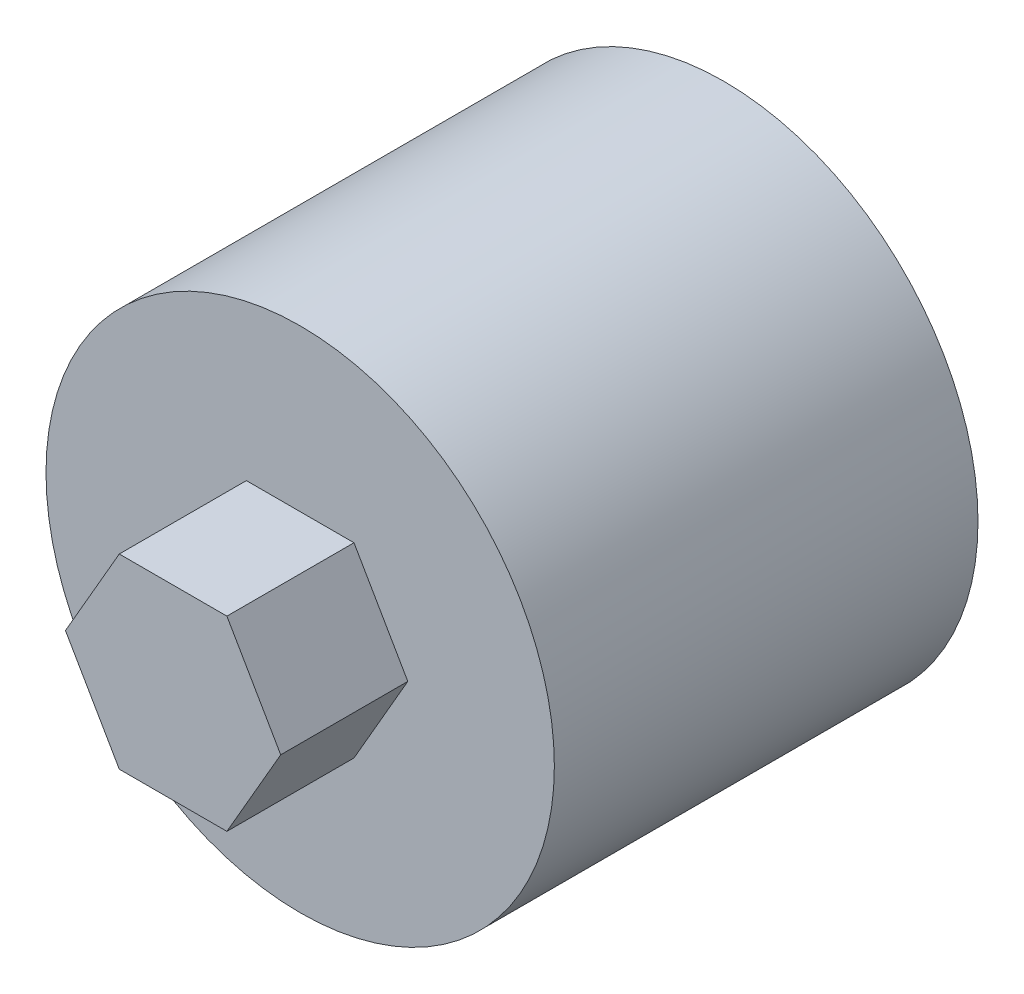
SolidWorks part; units mm, degrees
ref_plane "前视基准面" through (0, 0, 0) normal (0, 0, 1) x (1, 0, 0)
ref_plane "上视基准面" through (0, 0, 0) normal (0, 1, 0) x (1, 0, 0)
ref_plane "右视基准面" through (0, 0, 0) normal (1, 0, 0) x (0, 0, -1)
other "Configuration Table"
sketch "草图1" plane through (0, 0, 0) normal (0, 0, 1) x (1, 0, 0)
  line L0 (0, 0) -> (1.7387, 0.4659) construction
  line L1 (0, 0) -> (1.6291, 0.4551)
  line L2 (0, 0) -> (1.6291, -0.4551)
  line L3 (0, 0) -> (1.7387, -0.4659) construction
  line L4 (0, 0) -> (2.425, 0) construction
  line L5 (1.7387, 0.4659) -> (1.7387, -0.4659) construction
  circle A0 centre (0, 0) radius 1.525
  circle A1 centre (0, 0) radius 2.425
  circle A2 centre (0, 0) radius 1.6914 construction
  circle A3 centre (0, 0) radius 1.8 construction
  circle A4 centre (0, 0) radius 3
  spline S0 degree 4 poles (1.6291, 0.4551) (1.6415, 0.4586) (1.6769, 0.4656) (1.746, 0.4684) (1.8576, 0.4574) (1.9985, 0.4209) (2.171, 0.3489) (2.3582, 0.2351) (2.5438, 0.0819) (2.7191, -0.1093) (2.8693, -0.3205) (2.9946, -0.5472) (3.1006, -0.7975) (3.1986, -1.1195) (3.2658, -1.5159) (3.2754, -1.9832) (3.2064, -2.4974) (3.0631, -2.9965) (2.8558, -3.471) (2.5865, -3.9159) (2.2706, -4.3232) (1.901, -4.6937) (1.507, -5.0164) (1.0559, -5.3028) (0.6986, -5.4883) (0.2793, -5.6591) (0.0342, -5.7399) (-0.2484, -5.8241) (-0.3932, -5.8525) (-0.5197, -5.8826) (-0.5587, -5.8884) (-0.5863, -5.894) (-0.6011, -5.8971) knots 0 0 0 0 0 0.005604 0.015718 0.02996 0.048734 0.068727 0.096889 0.125051 0.153212 0.181374 0.209535 0.237696 0.271429 0.327752 0.384075 0.440398 0.496721 0.553044 0.609367 0.66569 0.722013 0.778336 0.834659 0.890982 0.909091 0.954545 0.977273 0.988636 0.994318 1 1 1 1 1 construction
  spline S1 degree 4 poles (1.6291, 0.4551) (1.6415, 0.4586) (1.6769, 0.4656) (1.746, 0.4684) (1.8576, 0.4574) (1.9985, 0.4209) (2.171, 0.3489) (2.3582, 0.2351) (2.5438, 0.0819) (2.7191, -0.1093) (2.8693, -0.3205) (2.9946, -0.5472) (3.1006, -0.7975) (3.1986, -1.1195) (3.2658, -1.5159) (3.2754, -1.9832) (3.2064, -2.4974) (3.0631, -2.9965) (2.8558, -3.471) (2.5865, -3.9159) (2.2706, -4.3232) (1.901, -4.6937) (1.507, -5.0164) (1.0559, -5.3028) (0.6986, -5.4883) (0.3874, -5.615) (0.2408, -5.6686) (0.2052, -5.6811) knots 0 0 0 0 0 0.005604 0.015718 0.02996 0.048734 0.068727 0.096889 0.125051 0.153212 0.181374 0.209535 0.237696 0.271429 0.327752 0.384075 0.440398 0.496721 0.553044 0.609367 0.66569 0.722013 0.778336 0.834659 0.890982 0.909091 0.909091 0.909091 0.909091 0.909091
  spline S2 degree 4 poles (1.6291, -0.4551) (1.6415, -0.4586) (1.6769, -0.4656) (1.746, -0.4684) (1.8576, -0.4574) (1.9985, -0.4209) (2.171, -0.3489) (2.3582, -0.2351) (2.5438, -0.0819) (2.7191, 0.1093) (2.8693, 0.3205) (2.9946, 0.5472) (3.1006, 0.7975) (3.1986, 1.1195) (3.2658, 1.5159) (3.2754, 1.9832) (3.2064, 2.4974) (3.0631, 2.9965) (2.8558, 3.471) (2.5865, 3.9159) (2.2706, 4.3232) (1.901, 4.6937) (1.507, 5.0164) (1.0559, 5.3028) (0.6986, 5.4883) (0.2793, 5.6591) (0.0342, 5.7399) (-0.2484, 5.8241) (-0.3932, 5.8525) (-0.5197, 5.8826) (-0.5587, 5.8884) (-0.5863, 5.894) (-0.6011, 5.8971) knots 0 0 0 0 0 0.005604 0.015718 0.02996 0.048734 0.068727 0.096889 0.125051 0.153212 0.181374 0.209535 0.237696 0.271429 0.327752 0.384075 0.440398 0.496721 0.553044 0.609367 0.66569 0.722013 0.778336 0.834659 0.890982 0.909091 0.954545 0.977273 0.988636 0.994318 1 1 1 1 1 construction
  spline S3 degree 4 poles (1.6291, -0.4551) (1.6415, -0.4586) (1.6769, -0.4656) (1.746, -0.4684) (1.8576, -0.4574) (1.9985, -0.4209) (2.171, -0.3489) (2.3582, -0.2351) (2.5438, -0.0819) (2.7191, 0.1093) (2.8693, 0.3205) (2.9946, 0.5472) (3.1006, 0.7975) (3.1986, 1.1195) (3.2658, 1.5159) (3.2754, 1.9832) (3.2064, 2.4974) (3.0631, 2.9965) (2.8558, 3.471) (2.5865, 3.9159) (2.2706, 4.3232) (1.901, 4.6937) (1.507, 5.0164) (1.0559, 5.3028) (0.6986, 5.4883) (0.3874, 5.615) (0.2408, 5.6686) (0.2052, 5.6811) knots 0 0 0 0 0 0.005604 0.015718 0.02996 0.048734 0.068727 0.096889 0.125051 0.153212 0.181374 0.209535 0.237696 0.271429 0.327752 0.384075 0.440398 0.496721 0.553044 0.609367 0.66569 0.722013 0.778336 0.834659 0.890982 0.909091 0.909091 0.909091 0.909091 0.909091
  point P16 (1.7387, 0)
  dimension "内啮合齿顶圆直径" = 3.05
  dimension "内啮合分度圆直径" = 3.6
  dimension "内啮合基圆直径" = 3.3829
  dimension "内啮合齿根圆直径" = 4.85
  dimension "外径" = 6
  dimension "渐开线镜像线夹角" = 15
extrude "凸台-拉伸1" add sketch "草图1" along normal blind 4 contours A4 | A0
extrude "切除-拉伸2" cut sketch "草图1<3>" along normal through all contours A0 S3 A1 S1 region at (1.9135, 0, 0)
sketch "草图1<3>" plane through (0, 0, 0) normal (0, 0, 1) x (1, 0, 0) same geometry as "草图1"
pattern_circular "阵列(圆周)1" count 9 over 360 about axis through (0, 0, 4) along (0, 0, 1) of "切除-拉伸2"
sketch "草图2" plane through (0, 0, 4) normal (0, 0, 1) x (1, 0, 0)
  line L1 (0.6351, 1.1) -> (-0.6351, 1.1)
  line L2 (-0.6351, 1.1) -> (-1.2702, 0)
  line L3 (-1.2702, 0) -> (-0.6351, -1.1)
  line L4 (-0.6351, -1.1) -> (0.6351, -1.1)
  line L5 (0.6351, -1.1) -> (1.2702, 0)
  line L6 (1.2702, 0) -> (0.6351, 1.1)
  circle A0 centre (0, 0) radius 3
  circle A1 centre (0, 0) radius 3 construction
  circle A2 centre (0, 0) radius 1.2702
  circle A3 centre (0, 0) radius 1.1 construction
  dimension "D1" = 2.2
extrude "凸台-拉伸2" add sketch "草图2" along normal blind 1 contours A0
extrude "凸台-拉伸3" add sketch "草图2<3>" along normal blind 1.5 from surface contours L1 L2 L3 L4 L5 L6 starting at face at (3, 0, 5)
sketch "草图2<3>" plane through (0, 0, 4) normal (0, 0, 1) x (1, 0, 0) same geometry as "草图2"
equation "\"m\"= 0.4'模数"
equation "\"z1\"= 6'外啮合齿轮数"
equation "\"a\"= 20度'压力角"
equation "\"z2\"= 9'内啮合齿轮数"
equation "\"hax\"= 1'齿顶高系数"
equation "\"cx\"= 0.25'顶隙系数"
equation "\"ha\"= \"hax\" * \"m\"'齿顶高"
equation "\"hf\"= ( \"hax\" + \"cx\" ) * \"m\"'齿根高"
equation "\"d1\"= \"m\" * \"z1\"'外啮合分度圆直径"
equation "\"da1\"= ( \"z1\" + 2 ) * \"m\"'外啮合齿顶圆直径"
equation "\"df1\"= \"d1\" - 2 * \"hf\"'外啮合齿根圆直径"
equation "\"db1\"= \"d1\" * cos ( \"a\" )'外啮合基圆直径"
equation "\"p\"= \"m\" * PI'齿距"
equation "\"d2\"= \"m\" * \"z2\"'内啮合分度圆直径"
equation "\"db2\"= \"d2\" * cos ( \"a\" )'内啮合基圆直径"
equation "\"da2\"= ( \"z2\" - 2 ) * \"m\"'内啮合齿顶圆直径"
equation "\"df2\"= \"d2\" + 2 * \"hf\"'内啮合齿根圆直径"
equation "\"内啮合齿顶圆直径@草图1\" = \"da2\" + 0.5 * \"hf\""
equation "\"内啮合齿根圆直径@草图1\"= \"df2\" + 0.5 * \"hf\""
equation "\"内啮合分度圆直径@草图1\"= \"d2\""
equation "\"内啮合基圆直径@草图1\"= \"db2\""
equation "\"渐开线镜像线夹角@草图1\"= 360度 / 4 / \"z2\" + 360度 / 4 / \"z2\" / 2"
equation "\"do\"= IIF ( \"edo\" >= ( \"df2\" + 1 ) , \"edo\" , ( \"df2\" + 1 ) )'外圈直径"
equation "\"h\"= 4'厚度"
equation "\"外径@草图1\"= \"do\""
equation "\"厚度@凸台-拉伸1\"= \"h\""
equation "\"内啮合齿轮数@阵列(圆周)1\"= \"z2\""
equation "\"edo\"= 6'期望的外圈直径"
